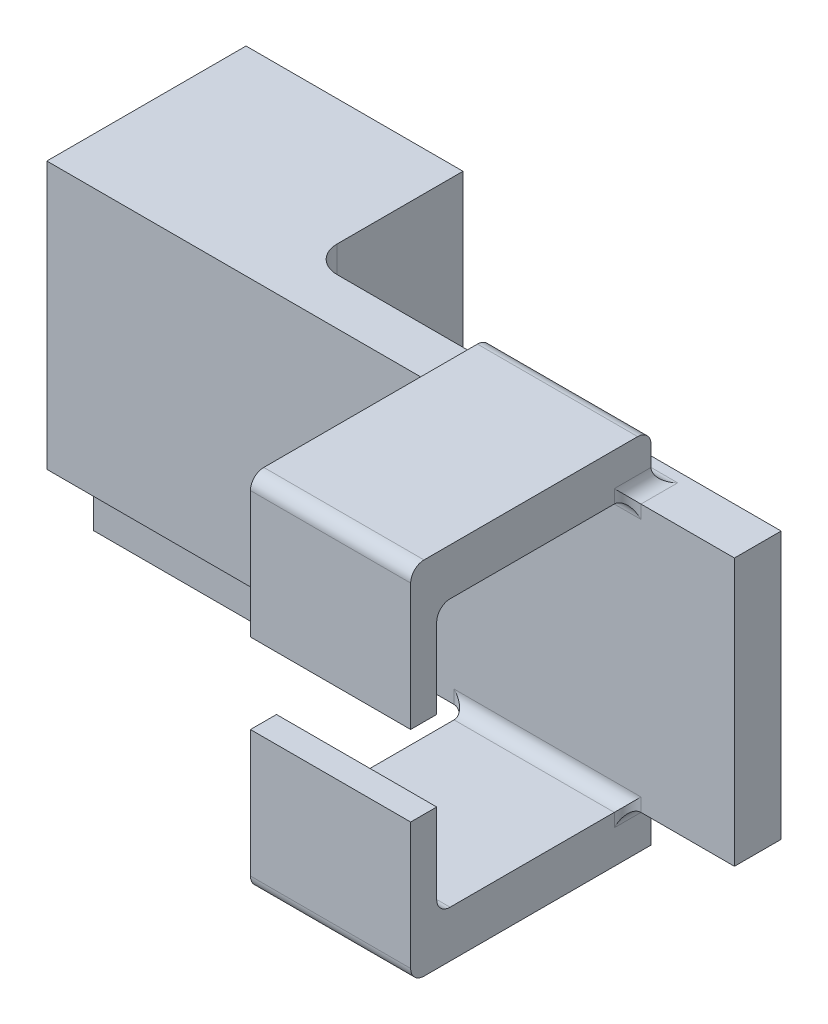
SolidWorks part; units mm, degrees
ref_plane "Front Plane" through (0, 0, 0) normal (0, 0, 1) x (1, 0, 0)
ref_plane "Top Plane" through (0, 0, 0) normal (0, 1, 0) x (1, 0, 0)
ref_plane "Right Plane" through (0, 0, 0) normal (1, 0, 0) x (0, 0, -1)
sketch "Sketch1" plane through (0, 0, 0) normal (0, 0, 1) x (1, 0, 0)
  line L1 (-25.75, 10) -> (25.75, 10)
  line L2 (-25.75, 10) -> (-25.75, -10)
  line L3 (-25.75, -10) -> (25.75, -10)
  line L4 (25.75, 10) -> (25.75, -10)
  line L5 (-25.75, 10) -> (25.75, -10) construction
  line L6 (-25.75, -10) -> (25.75, 10) construction
  point P0 (0, 0)
  dimension "D1" = 51.5
  dimension "D2" = 20
extrude "Boss-Extrude1" add sketch "Sketch1" along normal blind 3.5
sketch "Sketch2" plane through (0, 10, 0) normal (0, 1, 0) x (1, 0, 0)
  line L0 (25.75, -3.5) -> (25.75, 0) construction
  line L1 (17.75, -1.75) -> (5.75, -1.75)
  line L2 (17.75, -1.75) -> (17.75, -19.75)
  line L3 (17.75, -19.75) -> (5.75, -19.75)
  line L4 (5.75, -1.75) -> (5.75, -19.75)
  line L5 (25.75, 0) -> (-25.75, 0) construction
  dimension "D1" = 12
  dimension "D2" = 18
  dimension "D3" = 8
  dimension "D4" = 1.75
extrude "Boss-Extrude2" add sketch "Sketch2" along normal blind 3.5
fillet "Fillet1" radius 1 1 edges at (11.75, 10, 1.75)
fillet "Fillet2" radius 1 1 edges at (11.75, 10, 3.5)
sketch "Sketch3" plane through (0, -10, 0) normal (0, -1, 0) x (-1, 0, 0)
  line L0 (25.75, 0) -> (-25.75, 0) construction
  line L1 (-17.75, -1.75) -> (-5.75, -1.75)
  line L2 (-17.75, -1.75) -> (-17.75, -19.75)
  line L3 (-17.75, -19.75) -> (-5.75, -19.75)
  line L4 (-5.75, -1.75) -> (-5.75, -19.75)
  line L5 (-25.75, -3.5) -> (-25.75, 0) construction
  dimension "D1" = 12
  dimension "D2" = 1.75
  dimension "D3" = 8
  dimension "D4" = 18
extrude "Boss-Extrude3" add sketch "Sketch3" along normal blind 3.5
fillet "Fillet3" radius 1 1 edges at (11.75, -10, 1.75)
fillet "Fillet4" radius 1 1 edges at (11.75, -10, 3.5)
fillet "Fillet5" radius 1 1 edges at (17.75, 10, 2.125)
fillet "Fillet6" radius 1 1 edges at (5.75, 10, 2.125)
fillet "Fillet7" radius 1 1 edges at (17.75, 10, 3.5)
fillet "Fillet8" radius 1 1 edges at (5.75, 10, 3.5)
fillet "Fillet9" radius 1 1 edges at (5.75, -10, 2.125)
fillet "Fillet10" radius 1 1 edges at (5.75, -10, 3.5)
fillet "Fillet11" radius 1 1 edges at (17.75, -10, 2.125)
fillet "Fillet12" radius 1 1 edges at (17.75, -10, 3.5)
sketch "Sketch4" plane through (0, -10, 0) normal (0, 1, 0) x (1, 0, 0)
  line L0 (17.75, -4.5) -> (17.75, -19.75) construction
  line L1 (5.75, -19.75) -> (17.75, -19.75)
  line L2 (5.75, -19.75) -> (5.75, -17.8)
  line L3 (5.75, -17.8) -> (17.75, -17.8)
  line L4 (17.75, -19.75) -> (17.75, -17.8)
  dimension "D1" = 1.95
  dimension "D2" = 12
extrude "Boss-Extrude4" add sketch "Sketch4" along normal blind 7
sketch "Sketch5" plane through (0, 10, 0) normal (0, -1, 0) x (-1, 0, 0)
  line L0 (-17.75, -19.75) -> (-17.75, -4.5) construction
  line L1 (-5.75, -19.75) -> (-17.75, -19.75)
  line L2 (-5.75, -19.75) -> (-5.75, -17.8)
  line L3 (-5.75, -17.8) -> (-17.75, -17.8)
  line L4 (-17.75, -19.75) -> (-17.75, -17.8)
  dimension "D1" = 12
  dimension "D2" = 1.95
extrude "Boss-Extrude5" add sketch "Sketch5" along normal blind 7
fillet "Fillet13" radius 1 1 edges at (11.75, 10, 17.8)
fillet "Fillet14" radius 1 1 edges at (11.75, 13.5, 19.75)
fillet "Fillet15" radius 1 1 edges at (11.75, 13.5, 1.75)
fillet "Fillet16" radius 1 1 edges at (11.75, -13.5, 19.75)
fillet "Fillet17" radius 1 1 edges at (11.75, -10, 17.8)
sketch "Sketch8" plane through (0, 0, 0) normal (0, 0, -1) x (-1, 0, 0)
  line L7 (25.75, 10) -> (9.5, 10)
  line L8 (25.75, 10) -> (25.75, -15.7265)
  line L9 (25.75, -15.7265) -> (9.5, -15.7265)
  line L10 (9.5, 10) -> (9.5, -15.7265)
  dimension "D1" = 16.25
extrude "Boss-Extrude6" add sketch "Sketch8" along normal blind 11.42
fillet "Fillet21" radius 2 1 edges at (-9.5, 0, 0)
fillet "Fillet22" radius 2 1 edges at (-17.625, -10, 0)
fillet "Fillet23" radius 2 1 edges at (-9.5, -10, 0)
